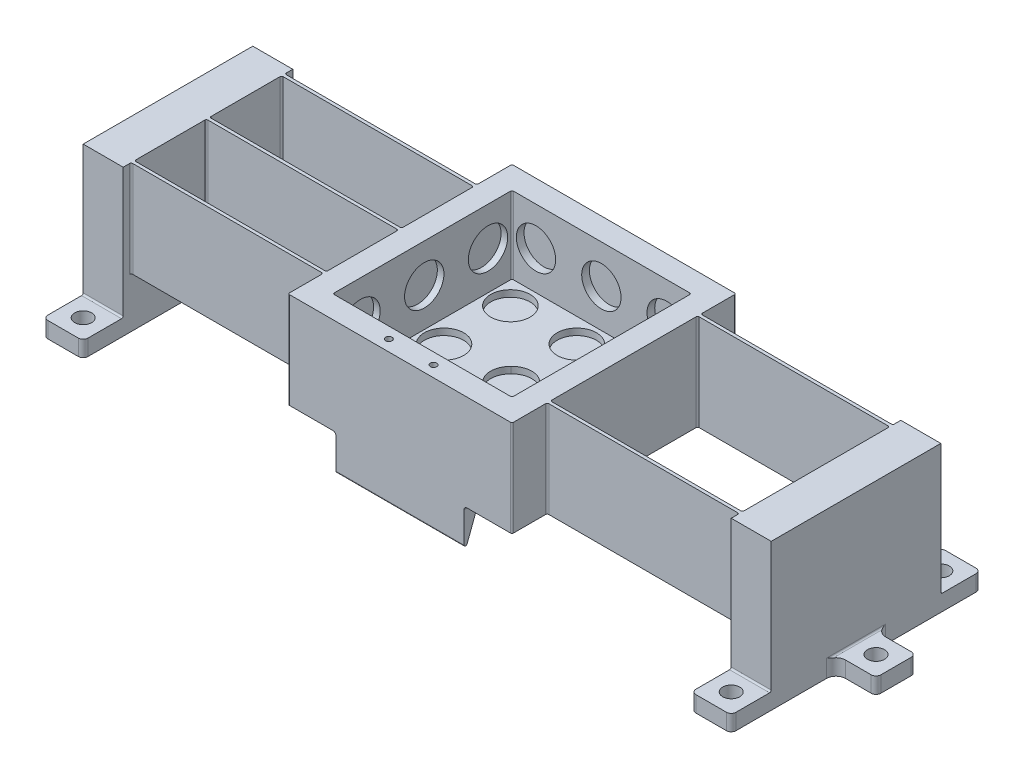
SolidWorks part; units mm, degrees
ref_plane "Front Plane" through (0, 0, 0) normal (0, 0, 1) x (1, 0, 0)
ref_plane "Top Plane" through (0, 0, 0) normal (0, 1, 0) x (1, 0, 0)
ref_plane "Right Plane" through (0, 0, 0) normal (1, 0, 0) x (0, 0, -1)
sketch "Sketch1" plane through (0, 0, 0) normal (0, 1, 0) x (1, 0, 0)
  line L1 (-35, -35) -> (35, -35)
  line L2 (-35, -35) -> (-35, 35)
  line L3 (-35, 35) -> (35, 35)
  line L4 (35, -35) -> (35, 35)
  line L5 (-35, -35) -> (35, 35) construction
  line L6 (-35, 35) -> (35, -35) construction
  point P0 (0, 0)
  dimension "D1" = 70
  dimension "D2" = 70
extrude "Boss-Extrude1" add sketch "Sketch1" along normal blind 30
shell "Shell1" thickness 7 removed face at (0, 30, 0)
sketch "Sketch2" plane through (0, 30, 0) normal (0, 1, 0) x (1, 0, 0)
  line L0 (-35, 35) -> (-35, -35) construction
  line L1 (-28, -28) -> (28, -28) construction
  line L2 (-28, -28) -> (-28, 28) construction
  line L3 (-28, 28) -> (28, 28) construction
  line L4 (28, -28) -> (28, 28) construction
  line L5 (-28, -28) -> (28, 28) construction
  line L6 (-28, 28) -> (28, -28) construction
  line L7 (35, 35) -> (-35, 35) construction
  point P0 (0, 0)
  dimension "D1" = 7
  dimension "D2" = 7
sketch "Sketch3" plane through (35, 0, 0) normal (1, 0, 0) x (0, 0, -1)
  line L0 (-35, 30) -> (35, 30) construction
  line L1 (-24, 30) -> (-23, 30)
  line L2 (-24, 30) -> (-24, 0)
  line L3 (-24, 0) -> (-23, 0)
  line L4 (-23, 30) -> (-23, 0)
  line L5 (-35, 0) -> (35, 0) construction
  line L6 (-28, 30) -> (28, 30) construction
  line L7 (-0.5, 30) -> (0.5, 30)
  line L8 (-0.5, 30) -> (-0.5, 0)
  line L9 (-0.5, 0) -> (0.5, 0)
  line L10 (0.5, 30) -> (0.5, 0)
  line L11 (28, 30) -> (-28, 30) construction
  line L12 (24, 30) -> (23, 30)
  line L13 (24, 30) -> (24, 0)
  line L14 (24, 0) -> (23, 0)
  line L15 (23, 30) -> (23, 0)
  line L16 (-23.5, 30) -> (-23.5, 0) construction
  line L17 (0, 30) -> (0, 0) construction
  line L18 (23.5, 0) -> (23.5, 30) construction
  dimension "D1" = 23
  dimension "D2" = 23
  dimension "D3" = 1
extrude "Boss-Extrude2" add sketch "Sketch3" along normal blind 60
sketch "Sketch5" plane through (95, 0, 0) normal (1, 0, 0) x (0, 0, -1)
  line L0 (-24, 30) -> (-24, 0) construction
  line L1 (-26.5, 30) -> (26.5, 30)
  line L2 (-26.5, 30) -> (-26.5, 0)
  line L3 (-26.5, 0) -> (26.5, 0)
  line L4 (26.5, 30) -> (26.5, 0)
  line L5 (28, 30) -> (-28, 30) construction
  line L6 (24, 0) -> (35, 0) construction
  line L7 (24, 0) -> (24, 30) construction
  dimension "D1" = 2.5
  dimension "D2" = 2.5
extrude "Boss-Extrude3" add sketch "Sketch5" along normal blind 12.5
sketch "Sketch6" plane through (0, 0, 0) normal (0, -1, 0) x (1, 0, 0)
  line L1 (95, 26.5) -> (107.5, 26.5)
  line L2 (95, 26.5) -> (95, -26.5)
  line L3 (95, -26.5) -> (107.5, -26.5)
  line L4 (107.5, 26.5) -> (107.5, -26.5)
extrude "Boss-Extrude4" add sketch "Sketch6" along normal blind 15.75
sketch "Sketch8" plane through (0, -15.75, 0) normal (0, -1, 0) x (1, 0, 0)
  line L1 (107.5, -26.5) -> (95, -26.5)
  line L2 (107.5, -26.5) -> (107.5, -39)
  line L3 (107.5, -39) -> (95, -39)
  line L4 (95, -26.5) -> (95, -39)
  line L5 (107.5, 26.5) -> (95, 26.5)
  line L6 (107.5, 26.5) -> (107.5, 39)
  line L7 (107.5, 39) -> (95, 39)
  line L8 (95, 26.5) -> (95, 39)
  line L13 (107.5, -26.5) -> (107.5, 26.5) construction
  line L14 (120, -6.25) -> (107.5, -6.25)
  line L15 (120, -6.25) -> (120, 6.25)
  line L16 (120, 6.25) -> (107.5, 6.25)
  line L17 (107.5, -6.25) -> (107.5, 6.25)
  line L18 (120, -6.25) -> (107.5, 6.25) construction
  line L19 (120, 6.25) -> (107.5, -6.25) construction
  line L20 (95, 0) -> (120, 0) construction
  line L21 (95, 0.5) -> (95, -0.5) construction
  point P13 (113.75, 0)
  point P19 (107.5, 0)
  point P20 (107.5, 0)
extrude "Boss-Extrude5" add sketch "Sketch8" against normal blind 5
hole_wizard "Ø5.0mm Dowel Hole1" positions "Sketch9" profile "Sketch10" hole size "Ø5.0" standard "ANSI Metric"
sketch "Sketch9" plane through (0, -10.75, 0) normal (0, 1, 0) x (1, 0, 0)
  line L0 (101.25, 39) -> (101.25, 32.75) construction
  line L1 (95, 39) -> (107.5, 39) construction
  line L2 (101.25, 32.75) -> (107.5, 32.75) construction
  line L3 (107.5, 39) -> (107.5, 26.5) construction
  line L5 (107.5, 0) -> (113.75, 0) construction
  line L6 (107.5, -6.25) -> (107.5, 6.25) construction
  line L7 (113.75, 0) -> (113.75, 6.25) construction
  line L8 (107.5, 6.25) -> (120, 6.25) construction
  line L10 (101.25, -26.5) -> (101.25, -32.75) construction
  line L11 (95, -26.5) -> (107.5, -26.5) construction
  line L12 (101.25, -32.75) -> (107.5, -32.75) construction
  line L13 (107.5, -26.5) -> (107.5, -39) construction
  point P0 (101.25, 32.75)
  point P2 (113.75, 0)
  point P4 (101.25, -32.75)
sketch "Sketch10" plane through (101.25, -10.75, -32.75) normal (1, 0, 0) x (0, 0, 1)
  line L0 (0, 0) -> (0, 18.1023)
  line L1 (0, 18.1023) -> (2.65, 16.51)
  line L2 (2.65, 16.51) -> (2.65, 0)
  line L5 (2.65, 0) -> (0, 0)
  line L10 (0, 18.1023) -> (-2.65, 16.51) construction
  line L11 (0, -6.35) -> (0, 107.95) construction
  dimension "Hole Dia." = 5.3
  dimension "Hole Depth" = 16.51
  dimension "Drill Angle" = 118
mirror "Mirror1" about plane through (0, 0, 0) normal (1, 0, 0) of "Boss-Extrude2", "Boss-Extrude3", "Boss-Extrude5", "Boss-Extrude4", "Ø5.0mm Dowel Hole1"
fillet "Fillet2" radius 1.5 12 edges at (120, -13.25, 6.25) (120, -13.25, -6.25) (107.5, -13.25, -39) (95, -13.25, -39) (107.5, -13.25, 39) (95, -13.25, 39) (-95, -13.25, -39) (-107.5, -13.25, -39) (-120, -13.25, -6.25) (-120, -13.25, 6.25) (-95, -13.25, 39) (-107.5, -13.25, 39)
sketch "Sketch11" plane through (0, 6, 0) normal (0, 1, 0) x (1, 0, 0)
  line L26 (-28, -28) -> (-28, 28) construction
  line L32 (-28, -28) -> (28, -28) construction
  circle A0 centre (-21, -21) radius 6.15
  dimension "D1" = 12.3
  dimension "D2" = 0.85
  dimension "D3" = 0.85
extrude "Cut-Extrude1" cut sketch "Sketch11" against normal blind 2.05
pattern_linear "LPattern1" count 3 spacing 20.75 along (1, 0, 0) count 3 spacing 20.75 along (0, 0, -1) of "Cut-Extrude1"
sketch "Sketch14" plane through (0, 6, 0) normal (0, 1, 0) x (1, 0, 0)
  line L0 (-28, 0) -> (0, 0) construction
  line L1 (-28, 28) -> (-28, -28) construction
  line L2 (0, 0) -> (0, -28) construction
  line L3 (-28, -28) -> (28, -28) construction
  circle A0 centre (0, 0) radius 6.15
  dimension "D1" = 12.3
extrude "Cut-Extrude4" cut sketch "Sketch14" against normal blind 2.05
sketch "Sketch12" plane through (-28, 0, 0) normal (1, 0, 0) x (0, 0, -1)
  line L5 (-28, 18) -> (-19.35, 18) construction
  line L6 (-28, 30) -> (-28, 6) construction
  circle A0 centre (-19.35, 18) radius 6.15
  dimension "D1" = 12.3
  dimension "D2" = 2.5
extrude "Cut-Extrude2" cut sketch "Sketch12" against normal blind 2.05
pattern_linear "LPattern2" count 3 spacing 19.925 along (0, 0, -1) of "Cut-Extrude2"
sketch "Sketch13" plane through (0, 0, -28) normal (0, 0, -1) x (-1, 0, 0)
  line L6 (-28, 30) -> (-28, 6) construction
  line L7 (-20.35, 18) -> (-28, 18) construction
  circle A0 centre (-20.35, 18) radius 6.15
  dimension "D1" = 12.3
  dimension "D3" = 1.5
extrude "Cut-Extrude3" cut sketch "Sketch13" along normal blind 2.4
pattern_linear "LPattern3" count 3 spacing 20.425 along (-1, 0, 0) of "Cut-Extrude3"
mirror "Mirror2" about plane through (0, 0, 0) normal (1, 0, 0) of "LPattern2", "Cut-Extrude2"
sketch "Sketch24" plane through (0, 30, 0) normal (0, 1, 0) x (1, 0, 0)
  line L1 (35, 0.5) -> (95, 0.5)
  line L2 (35, 0.5) -> (35, -0.5)
  line L3 (35, -0.5) -> (95, -0.5)
  line L4 (95, 0.5) -> (95, -0.5)
extrude "Cut-Extrude6" cut sketch "Sketch24" against normal through all both and the other way through all
fillet "Fillet4" radius 0.5 4 edges at (-35, 15, 35) (35, 15, 35) (-35, 15, -35) (35, 15, -35)
sketch "Sketch19" plane through (0, 0, 0) normal (1, 0, 0) x (0, 0, -1)
  line L0 (-30, 0) -> (-35, -13.25)
  line L1 (-35, -13.25) -> (-35, 0)
  line L2 (-35, 0) -> (-30, 0)
  line L3 (0, 0) -> (-30, 0) construction
  line L4 (37.5, -15.75) -> (-37.5, -15.75) construction
  dimension "D1" = 5
  dimension "D2" = 30
  dimension "D3" = 2.5
extrude "Boss-Extrude8" add sketch "Sketch19" along normal mid plane 40
sketch "Sketch20" plane through (0, 0, 0) normal (1, 0, 0) x (0, 0, -1)
  line L0 (-35, 20) -> (-42.5, 20)
  line L1 (-42.5, 20) -> (-42.5, 30)
  line L2 (-26.5, 30) -> (-42.5, 30) construction
  line L5 (-42.5, 30) -> (-40, 30)
  line L6 (-40, 30) -> (-40, 22.5)
  line L7 (-40, 22.5) -> (-35, 22.5)
  line L8 (-35, 22.5) -> (-35, 20)
  line L9 (-35, 30) -> (-35, 0) construction
  line L10 (-35, 0) -> (-35, 30) construction
  dimension "D1" = 5
  dimension "D2" = 10
  dimension "D3" = 2.5
  dimension "D4" = 2.5
extrude "Place For Sensor" [suppressed] add sketch "Sketch20" along normal mid plane 10
fillet "Place For Sensor Fillet5" [suppressed] radius 0.5
fillet "Place For Sensor Fillet6" [suppressed] radius 1.5
hole_wizard "Place For Sensor Ø3.0mm Dowel Hole2" [suppressed] positions "Sketch21" profile "Sketch22" hole size "Ø3.0" standard "ANSI Metric"
sketch "Sketch21" [suppressed] plane through (0, 0, 32.5) normal (0, 0, 1) x (1, 0, 0)
  line L0 (-2.5, 27.5) -> (2.5, 27.5) construction
  line L2 (-18, 30) -> (18, 30) construction
  line L3 (-5, 28.5) -> (-5, 20.5) construction
  line L4 (5, 28.5) -> (5, 20.5) construction
  point P0 (-2.5, 27.5)
  point P2 (2.5, 27.5)
  dimension "D1" = 2.5
  dimension "D2" = 2.5
  dimension "D3" = 2.5
sketch "Sketch22" plane through (-2.5, 27.5, 32.5) normal (1, 0, 0) x (0, -1, 0)
  line L0 (0, 0) -> (0, 2.5)
  line L1 (0, 2.5) -> (1.65, 2.5)
  line L2 (1.65, 2.5) -> (1.65, 0)
  line L5 (1.65, 0) -> (0, 0)
  line L11 (0, -6.35) -> (0, 107.95) construction
  dimension "Thru Hole Dia." = 3.3
  dimension "Thru Hole Depth" = 2.5
sketch "Sketch23" plane through (0, 30, 0) normal (0, 1, 0) x (1, 0, 0)
  line L1 (-28, -28) -> (28, -28) construction
  circle A0 centre (-7, -31.5) radius 1
  circle A1 centre (7, -31.5) radius 1
  dimension "D4" = 2
  dimension "D1" = 3.5
  dimension "D2" = 14
  dimension "D3" = 7
extrude "Cut-Extrude5" cut sketch "Sketch23" against normal blind 6
fillet "Fillet3" radius 0.5 4 edges at (28, 18, -28) (-28, 18, -28) (28, 18, 28) (-28, 18, 28)
fillet "Fillet1" radius 0.5 26 edges at (95, 15, 23) (95, 15, 24) (95, 15, -23) (95, 15, -24) (35, 15, 24) (35, 15, 23) (35, 15, -24) (35, 15, -23) (-95, 15, 24) (-95, 15, 23) (-95, 15, 0.5) (-95, 15, -0.5) (-95, 15, -24) (-95, 15, -23) (-35, 15, 24) (-35, 15, 23) (-35, 15, 0.5) (-35, 15, -0.5) (-35, 15, -23) (-35, 15, -24) (-101.25, -10.75, -26.5) (-107.5, -10.75, 0) (-101.25, -10.75, 26.5) (101.25, -10.75, 26.5) (101.25, -10.75, -26.5) (107.5, -10.75, 0)
fillet "Fillet5" radius 0.5 1 edges at (0, -13.25, 35)
fillet "Fillet6" radius 1 3 edges at (-20, 0, 32.5) (20, 0, 32.5) (0, 0, 30)
fillet "Fillet8" radius 3 4 edges at (107.5, -13, 6.25) (107.5, -13, -6.25) (-107.5, -13, -6.25) (-107.5, -13, 6.25)
